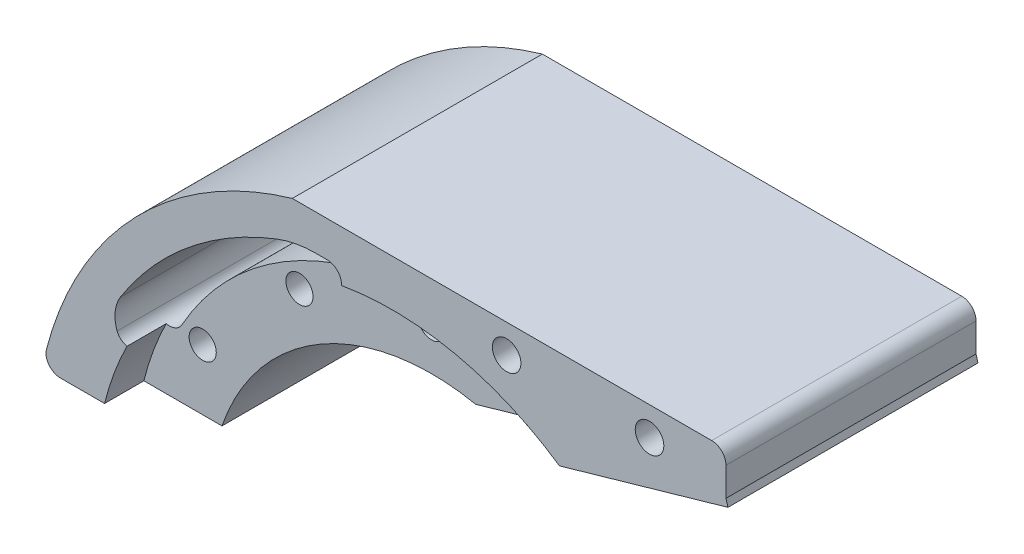
SolidWorks part; units mm, degrees
material "PBT 一般用途"
ref_plane "前视基准面" through (0, 0, 0) normal (0, 0, 1) x (1, 0, 0)
ref_plane "上视基准面" through (0, 0, 0) normal (0, 1, 0) x (1, 0, 0)
ref_plane "右视基准面" through (0, 0, 0) normal (1, 0, 0) x (0, 0, -1)
sketch "草图1" plane through (0, 0, 0) normal (0, 0, 1) x (1, 0, 0)
  line L0 (-54, 0) -> (54, 0) construction
  line L1 (0, 0) -> (0, 10) construction
  line L2 (-46.42, 26.4347) -> (-100.7026, 42)
  line L3 (46.42, 26.4347) -> (100.7026, 42)
  line L4 (-28.3826, 10) -> (28.3826, 10)
  line L5 (-100.7026, 42) -> (-100.7026, 48)
  line L6 (-100.7026, 48) -> (100.7026, 48)
  line L7 (100.7026, 48) -> (100.7026, 42)
  line L8 (-90, 44) -> (-70, 44) construction
  line L9 (90, 44) -> (70, 44) construction
  circle A0 centre (-54, 0) radius 26.5 construction
  circle A1 centre (54, 0) radius 26.5 construction
  arc A2 (-28.3826, 10) -> (-46.42, 26.4347) centre (-54, 0) ccw
  arc A3 (28.3826, 10) -> (46.42, 26.4347) centre (54, 0) cw
  circle A4 centre (-54, 0) radius 37 construction
  circle A5 centre (-54, 37) radius 1.9
  circle A6 centre (-35.5, 32.0429) radius 1.9
  circle A7 centre (-21.9571, 18.5) radius 1.9
  circle A8 centre (-17, 0) radius 1.9 construction
  circle A9 centre (17, 0) radius 1.9 construction
  circle A10 centre (21.9571, 18.5) radius 1.9
  circle A11 centre (35.5, 32.0429) radius 1.9
  circle A12 centre (54, 37) radius 1.9
  circle A13 centre (54, 0) radius 37 construction
  circle A14 centre (-90, 44) radius 2
  circle A15 centre (-70, 44) radius 2
  circle A16 centre (70, 44) radius 2
  circle A17 centre (90, 44) radius 2
  point P2 (0, 0)
  dimension "D2" = 53
  dimension "D3" = 55
  dimension "D8" = 74
  dimension "D9" = 3.8
  dimension "D11" = 20
  dimension "D13" = 4
  dimension "D1" = 108
  dimension "D4" = 16
  dimension "D5" = 10
  dimension "D6" = 6
  dimension "D7" = 38
  dimension "D12" = 70
  dimension "D14" = 4
  dimension "D10" = 4
extrude "凸台-拉伸1" add sketch "草图1" along normal blind 35
sketch "草图2" plane through (0, 0, 35) normal (0, 0, 1) x (1, 0, 0)
  line L0 (-100.7026, 42) -> (-100.9783, 41.0387)
  line L1 (-100.9783, 41.0387) -> (-67.3341, 31.3914)
  line L2 (-67.3341, 31.3914) -> (-67.0585, 32.3527)
  line L3 (-100.7026, 42) -> (-46.42, 26.4347) construction
  line L4 (-67.0585, 32.3527) -> (-100.7026, 42)
  line L5 (0, 10) -> (0, 48) construction
  line L6 (-28.3826, 10) -> (28.3826, 10) construction
  line L7 (100.7026, 48) -> (-100.7026, 48) construction
  line L8 (67.0585, 32.3527) -> (100.7026, 42)
  line L9 (67.3341, 31.3914) -> (67.0585, 32.3527)
  line L10 (100.9783, 41.0387) -> (67.3341, 31.3914)
  line L11 (100.7026, 42) -> (100.9783, 41.0387)
  dimension "D1" = 1
  dimension "D2" = 35
extrude "凸台-拉伸2" add sketch "草图2" against normal up to surface (35 mm away) up to face at (0, 32.1362, 0)
sketch "草图3" plane through (0, 0, 35) normal (0, 0, 1) x (1, 0, 0)
  line L1 (-6.6417, 40.2101) -> (-15.4766, 19.6585)
  line L3 (-10.8374, 17.7899) -> (-1.8374, 38.7258)
  line L4 (1.8374, 38.7258) -> (10.8374, 17.7899)
  line L5 (9, 15) -> (-9, 15)
  line L6 (-44.8896, 43) -> (-8.4792, 43)
  line L7 (100.7026, 48) -> (-100.7026, 48) construction
  line L8 (-28.3826, 10) -> (28.3826, 10) construction
  line L9 (0, 15) -> (0, 10) construction
  line L10 (44.8896, 43) -> (8.4792, 43)
  line L11 (6.6417, 40.2101) -> (15.4766, 19.6585)
  circle A0 centre (-54, 0) radius 40 construction
  arc A1 (-45.3234, 39.0476) -> (-19.0609, 19.4746) centre (-54, 0) cw
  arc A2 (-45.3234, 39.0476) -> (-44.8896, 43) centre (-44.8896, 41) cw
  arc A3 (10.8374, 17.7899) -> (9, 15) centre (9, 17) cw
  arc A4 (-10.8374, 17.7899) -> (-9, 15) centre (-9, 17) ccw
  arc A5 (-1.8374, 38.7258) -> (1.8374, 38.7258) centre (0, 37.9359) cw
  arc A6 (-8.4792, 43) -> (-6.6417, 40.2101) centre (-8.4792, 41) cw
  arc A7 (-19.0609, 19.4746) -> (-15.4766, 19.6585) centre (-17.314, 20.4484) ccw
  arc A8 (45.3234, 39.0476) -> (44.8896, 43) centre (44.8896, 41) ccw
  arc A9 (45.3234, 39.0476) -> (19.0609, 19.4746) centre (54, 0) ccw
  arc A10 (8.4792, 43) -> (6.6417, 40.2101) centre (8.4792, 41) ccw
  arc A11 (19.0609, 19.4746) -> (15.4766, 19.6585) centre (17.314, 20.4484) cw
  point P10 (0, 15)
  point P25 (0, 43)
  dimension "D1" = 80
  dimension "D2" = 5
  dimension "D4" = 2
  dimension "D6" = 2
  dimension "D3" = 5
  dimension "D5" = 5
  dimension "D7" = 18
extrude "切除-拉伸1" cut sketch "草图3" against normal through all
sketch "草图4" plane through (0, 0, 0) normal (0, 0, -1) x (-1, 0, 0)
  line L0 (0, 0) -> (0, 48) construction
  line L1 (-100.7026, 48) -> (100.7026, 48) construction
  circle A0 centre (54, 0) radius 41.5
  circle A1 centre (-54, 0) radius 41.5
  dimension "D1" = 83
extrude "切除-拉伸2" cut sketch "草图4" against normal blind 5.5
sketch "草图5" plane through (0, 0, 5.5) normal (0, 0, -1) x (-1, 0, 0)
  circle A0 centre (-54, 0) radius 31
  circle A1 centre (54, 0) radius 31
  dimension "D1" = 62
extrude "切除-拉伸3" cut sketch "草图5" against normal through all
sketch "草图6" plane through (0, 0, 0) normal (0, 0, -1) x (-1, 0, 0)
  line L0 (0, 0) -> (-54, 0) construction
  line L1 (-13.9839, 87.6552) -> (-42.2298, 48.5949)
  line L2 (-13.9839, 87.6552) -> (112.2367, 87.6552)
  line L3 (112.2367, 87.6552) -> (108.7339, 6.0131)
  line L4 (108.7339, 6.0131) -> (-4, 0)
  circle A0 centre (-54, 0) radius 50
  circle M3 centre (90, 44) radius 2
  circle M4 centre (70, 44) radius 2
  line M7 (-13.7228, 10) -> (13.7228, 10)
  arc M8 (13.7228, 10) -> (16.8528, 18.5023) centre (54, 0) cw
  arc M9 (16.8528, 18.5023) -> (15.4766, 19.6585) centre (17.314, 20.4484) cw
  line M10 (15.4766, 19.6585) -> (6.6417, 40.2101)
  arc M11 (6.6417, 40.2101) -> (8.4792, 43) centre (8.4792, 41) cw
  line M12 (8.4792, 43) -> (44.8896, 43)
  arc M13 (44.8896, 43) -> (46.8863, 40.8858) centre (44.8896, 41) cw
  arc M14 (46.8863, 40.8858) -> (77.3958, 34.2766) centre (54, 0) cw
  line M15 (77.3958, 34.2766) -> (100.9783, 41.0387)
  line M16 (100.9783, 41.0387) -> (100.7026, 42)
  line M17 (100.7026, 42) -> (100.7026, 48)
  line M18 (100.7026, 48) -> (-100.7026, 48)
  line M24 (-44.8896, 43) -> (-8.4792, 43)
  arc M25 (-8.4792, 43) -> (-6.6417, 40.2101) centre (-8.4792, 41) cw
  line M26 (-6.6417, 40.2101) -> (-15.4766, 19.6585)
  line M29 (9, 15) -> (-9, 15)
  line M31 (-10.8374, 17.7899) -> (-1.8374, 38.7258)
  arc M32 (-1.8374, 38.7258) -> (1.8374, 38.7258) centre (0, 37.9359) cw
  line M33 (1.8374, 38.7258) -> (10.8374, 17.7899)
  arc M34 (10.8374, 17.7899) -> (9, 15) centre (9, 17) cw
  dimension "D1" = 100
extrude "切除-拉伸4" cut sketch "草图6" against normal blind 90 contours A0 L4 L3 L2 L1 M18 M17 M16 M15 M14 M13 M12 M11 M10 M9 M8 M7 | A0 M7 M8 M9 M10 M11 M12 M13 M14 M15 M16 M17 M18 M24 M25 M26 M31 M32 M33 M34 M29 M3 M4 region at (-47.6595, 48.71, 0) region at (-30.3513, 46.5399, 0)
sketch "草图7" plane through (0, 0, 0) normal (0, 0, -1) x (-1, 0, 0)
  line L0 (0, 0) -> (-54, 0) construction
  line L1 (-40, 48) -> (-68, 48)
  line L2 (-100.7026, 48) -> (-40, 48) construction
  line L3 (-67.3341, 31.3914) -> (-100.9783, 41.0387)
  line L4 (-28.4853, 43) -> (-44.8896, 43)
  line L5 (-5.0102, 10) -> (-24.6572, 10)
  circle A0 centre (-54, 0) radius 40
  arc A1 (-19.0609, 19.4746) -> (-45.3234, 39.0476) centre (-54, 0) ccw construction
  circle A2 centre (-54, 0) radius 41.5
  arc A3 (-46.8863, 40.8858) -> (-77.3958, 34.2766) centre (-54, 0) ccw construction
  circle A4 centre (-54, 0) radius 50
  circle A5 centre (-54, 0) radius 45
  dimension "D1" = 5
extrude "凸台-拉伸3" add sketch "草图7" against normal up to surface (35 mm away) contours A5 L5 A4 L4 region at (18.3122, 28.5978, 0) up to face at (68, 44, 35)
fillet "圆角1" radius 15 1 edges at (40.7335, 43, 17.5)
fillet "圆角2" radius 5 1 edges at (14.5897, 21.7216, 17.5)
fillet "圆角3" radius 2 2 edges at (5.0102, 10, 17.5) (100.7026, 48, 17.5)
sketch "草图8" plane through (0, 0, 35) normal (0, 0, 1) x (1, 0, 0)
  line L4 (60.1748, 30.3788) -> (67.0585, 32.3527)
  line L5 (13.7228, 10) -> (24.6572, 10)
  line L6 (67.3341, 31.3914) -> (77.3958, 34.2766)
  line L7 (67.0585, 32.3527) -> (67.3341, 31.3914)
  line L8 (60.1748, 30.3788) -> (67.0585, 32.3527)
  line L9 (13.7228, 10) -> (24.6572, 10)
  line L10 (67.3341, 31.3914) -> (77.3958, 34.2766)
  line L11 (67.0585, 32.3527) -> (67.3341, 31.3914)
  arc A6 (60.1748, 30.3788) -> (24.6572, 10) centre (54, 0) ccw
  arc A7 (16.8528, 18.5023) -> (13.7228, 10) centre (54, 0) ccw
  arc A8 (16.8528, 18.5023) -> (19.0609, 19.4746) centre (17.314, 20.4484) ccw
  arc A9 (45.3234, 39.0476) -> (19.0609, 19.4746) centre (54, 0) ccw
  arc A10 (45.3234, 39.0476) -> (46.8863, 40.8858) centre (44.8896, 41) ccw
  arc A11 (77.3958, 34.2766) -> (46.8863, 40.8858) centre (54, 0) ccw
  arc A12 (60.1748, 30.3788) -> (24.6572, 10) centre (54, 0) ccw
  arc A13 (16.8528, 18.5023) -> (13.7228, 10) centre (54, 0) ccw
  arc A14 (16.8528, 18.5023) -> (19.0609, 19.4746) centre (17.314, 20.4484) ccw
  arc A15 (45.3234, 39.0476) -> (19.0609, 19.4746) centre (54, 0) ccw
  arc A16 (45.3234, 39.0476) -> (46.8863, 40.8858) centre (44.8896, 41) ccw
  arc A17 (77.3958, 34.2766) -> (46.8863, 40.8858) centre (54, 0) ccw
  dimension "D1" = 0
extrude "切除-拉伸5" cut sketch "草图8" against normal blind 5.5
sketch "草图9" plane through (0, 0, 5.5) normal (0, 0, -1) x (-1, 0, 0)
  line L4 (-67.0585, 32.3527) -> (-60.1748, 30.3788)
  line L5 (-24.6572, 10) -> (-13.7228, 10)
  line L6 (-77.3958, 34.2766) -> (-67.3341, 31.3914)
  line L7 (-67.3341, 31.3914) -> (-67.0585, 32.3527)
  line L8 (-67.0585, 32.3527) -> (-60.1748, 30.3788)
  line L9 (-24.6572, 10) -> (-13.7228, 10)
  line L10 (-77.3958, 34.2766) -> (-67.3341, 31.3914)
  line L11 (-67.3341, 31.3914) -> (-67.0585, 32.3527)
  circle A0 centre (-54, 37) radius 1.9 construction
  circle A1 centre (-35.5, 32.0429) radius 1.9 construction
  circle A2 centre (-21.9571, 18.5) radius 1.9 construction
  circle A3 centre (-54, 37) radius 1.9
  circle A4 centre (-35.5, 32.0429) radius 1.9
  circle A5 centre (-21.9571, 18.5) radius 1.9
  arc A6 (-24.6572, 10) -> (-60.1748, 30.3788) centre (-54, 0) ccw
  arc A7 (-13.7228, 10) -> (-16.8528, 18.5023) centre (-54, 0) ccw
  arc A8 (-19.0609, 19.4746) -> (-16.8528, 18.5023) centre (-17.314, 20.4484) ccw
  arc A9 (-19.0609, 19.4746) -> (-45.3234, 39.0476) centre (-54, 0) ccw
  arc A10 (-46.8863, 40.8858) -> (-45.3234, 39.0476) centre (-44.8896, 41) ccw
  arc A11 (-46.8863, 40.8858) -> (-77.3958, 34.2766) centre (-54, 0) ccw
  arc A12 (-24.6572, 10) -> (-60.1748, 30.3788) centre (-54, 0) ccw
  arc A13 (-13.7228, 10) -> (-16.8528, 18.5023) centre (-54, 0) ccw
  arc A14 (-19.0609, 19.4746) -> (-16.8528, 18.5023) centre (-17.314, 20.4484) ccw
  arc A15 (-19.0609, 19.4746) -> (-45.3234, 39.0476) centre (-54, 0) ccw
  arc A16 (-46.8863, 40.8858) -> (-45.3234, 39.0476) centre (-44.8896, 41) ccw
  arc A17 (-46.8863, 40.8858) -> (-77.3958, 34.2766) centre (-54, 0) ccw
  dimension "D1" = 0
extrude "凸台-拉伸4" add sketch "草图9" along normal up to surface (5.5 mm away) up to face at (47.5176, 33.2988, 0)
